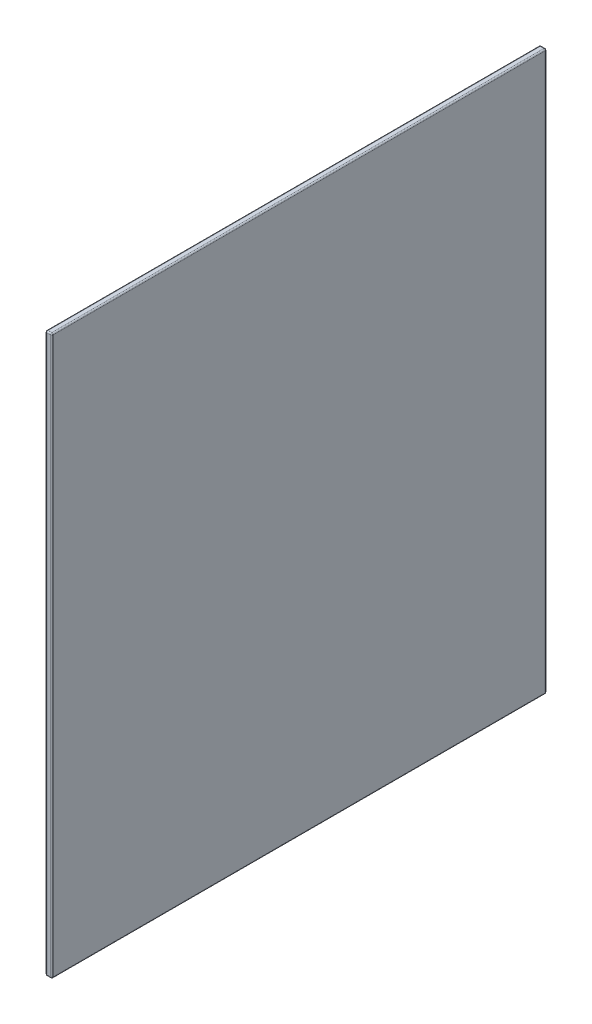
SolidWorks part; units mm, degrees
material "1023 Carbon Steel Sheet (SS)"
ref_plane "Front Plane" through (0, 0, 0) normal (0, 0, 1) x (1, 0, 0)
ref_plane "Top Plane" through (0, 0, 0) normal (0, 1, 0) x (1, 0, 0)
ref_plane "Right Plane" through (0, 0, 0) normal (1, 0, 0) x (0, 0, -1)
sketch "Sketch1" plane through (0, 0, 0) normal (1, 0, 0) x (0, 0, -1)
  line L1 (-184.15, -207.9625) -> (184.15, -207.9625)
  line L2 (-184.15, -207.9625) -> (-184.15, 207.9625)
  line L3 (-184.15, 207.9625) -> (184.15, 207.9625)
  line L4 (184.15, -207.9625) -> (184.15, 207.9625)
  line L5 (-184.15, -207.9625) -> (184.15, 207.9625) construction
  line L6 (-184.15, 207.9625) -> (184.15, -207.9625) construction
  point P0 (0, 0)
  dimension "D1" = 368.3
  dimension "D2" = 415.925
extrude "Boss-Extrude1" add sketch "Sketch1" along normal blind 4.7625
fillet "Fillet1" radius 1.016 8 edges at (0, 207.9625, 0) (0, 0, 184.15) (0, -207.9625, 0) (0, 0, -184.15) (4.7625, -207.9625, 0) (4.7625, 0, 184.15) (4.7625, 207.9625, 0) (4.7625, 0, -184.15)
fillet "Fillet2" radius 1.016 12 edges at (4.4649, 207.6649, -183.8524) (0.2976, 207.6649, -183.8524) (4.4649, -207.6649, -183.8524) (0.2976, -207.6649, -183.8524) (4.4649, -207.6649, 183.8524) (0.2976, -207.6649, 183.8524) (4.4649, 207.6649, 183.8524) (0.2976, 207.6649, 183.8524) (2.3813, 207.9625, -184.15) (2.3813, -207.9625, -184.15) (2.3813, -207.9625, 184.15) (2.3813, 207.9625, 184.15)
